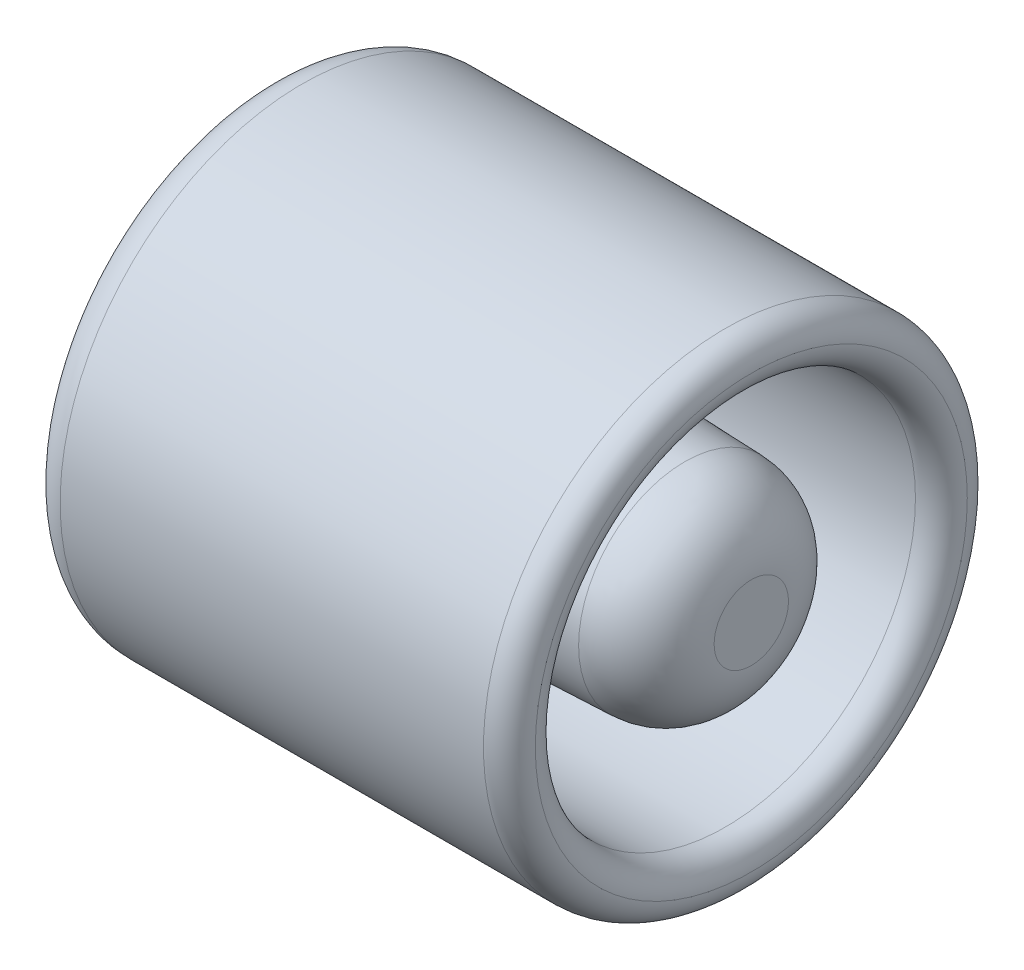
SolidWorks part; units mm, degrees
ref_plane "Piano frontale" through (0, 0, 0) normal (0, 0, 1) x (1, 0, 0)
ref_plane "Piano superiore" through (0, 0, 0) normal (0, 1, 0) x (1, 0, 0)
ref_plane "Piano destro" through (0, 0, 0) normal (1, 0, 0) x (0, 0, -1)
sketch "Schizzo1" plane through (0, 0, 0) normal (0, 0, 1) x (1, 0, 0)
  line L0 (-5.2956, 0) -> (7.171, 0) construction
  line L1 (0, 1.7349) -> (0, -2.3211) construction
  line L2 (0, 1.2) -> (0, 3.5)
  line L3 (0, 3.5) -> (2, 3.5)
  line L4 (2, 3.5) -> (2, 1.6921)
  line L6 (7, 1.5) -> (7, 0)
  line L7 (7, 0) -> (6, 0)
  line L11 (6, 1.2) -> (6, 0)
  line L12 (0, 1.2) -> (6, 1.2)
  line L13 (6, 1.5) -> (6, 0) construction
  line L16 (2, 1.6921) -> (7, 1.5)
  point P13 (0, 1.75)
  point P14 (6, 1.75)
  dimension "D1" = 7
  dimension "D2" = 3.5
  dimension "D3" = 1.5
  dimension "D4" = 2
  dimension "D5" = 2.2
  dimension "D7" = 1.2
  dimension "D6" = 1
revolve "Rivoluzione1" add sketch "Schizzo1" angle 360 about L0
sketch "Schizzo2" plane through (2, 0, 0) normal (1, 0, 0) x (0, 0, -1)
  circle A0 centre (0, 0) radius 2.75
  circle A1 centre (0, 0) radius 3.5
  dimension "D1" = 5.5
  dimension "D2" = 0.75
extrude "Estrusione-Estrusione1" add sketch "Schizzo2" along normal blind 5
fillet "Raccordo2" radius 0.1 1 edges at (0, 0, 1.2)
fillet "Raccordo3" radius 0.2 1 edges at (6, 0, 1.2)
fillet "Raccordo6" radius 1 1 edges at (7, 0, 1.5)
fillet "Raccordo7" radius 0.375 2 edges at (7, 0, -3.5) (7, 0, -2.75)
fillet "Raccordo8" radius 0.5 3 edges at (2, 0, -2.75) (0, 0, 3.5) (2, 0, 1.6921)
